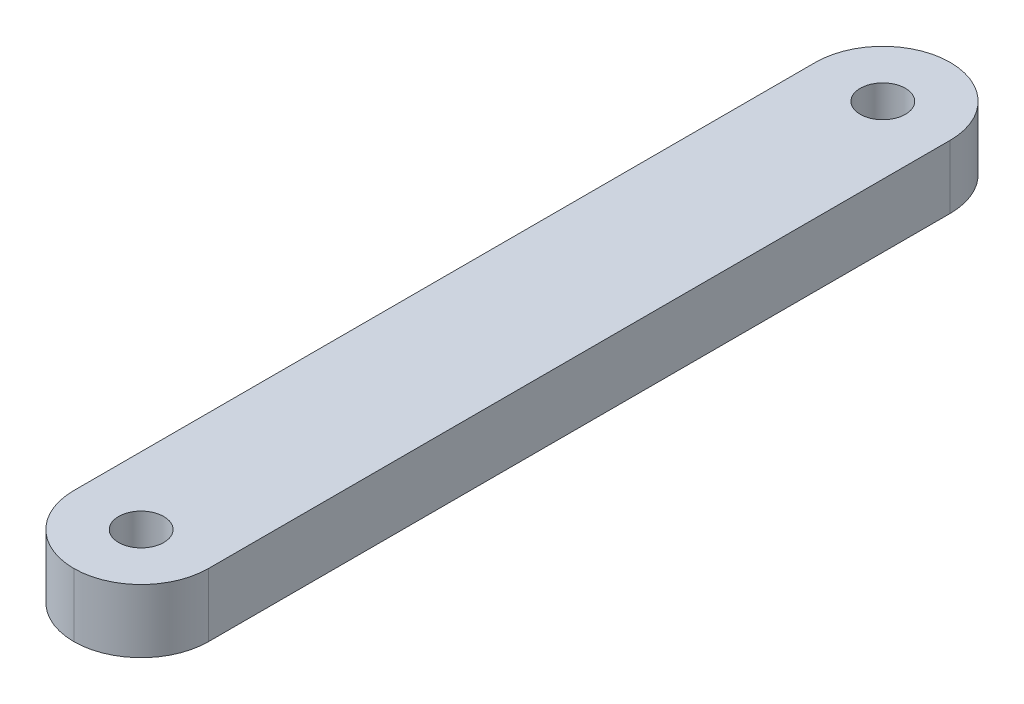
SolidWorks part; units mm, degrees
ref_plane "前视基准面" through (0, 0, 0) normal (0, 0, 1) x (1, 0, 0)
ref_plane "上视基准面" through (0, 0, 0) normal (0, 1, 0) x (1, 0, 0)
ref_plane "右视基准面" through (0, 0, 0) normal (1, 0, 0) x (0, 0, -1)
sketch "草图1" plane through (0, 0, 0) normal (0, 0, 1) x (1, 0, 0)
  line L1 (0, 0) -> (10, 0)
  line L2 (0, 0) -> (0, 5)
  line L3 (0, 5) -> (10, 5)
  line L4 (10, 0) -> (10, 5)
  dimension "D1" = 5
  dimension "D2" = 10
extrude "凸台-拉伸1" add sketch "草图1" along normal blind 65
sketch "草图2" plane through (0, 5, 0) normal (0, 1, 0) x (1, 0, 0)
  line L0 (10, 0) -> (0, 0) construction
  line L1 (10, -65) -> (10, 0) construction
  line L2 (10, -65) -> (0, -65) construction
  circle A0 centre (5, -5) radius 1.675
  circle A1 centre (5, -60) radius 1.675
  dimension "D1" = 3.35
  dimension "D2" = 3.35
  dimension "D3" = 5
  dimension "D4" = 5
  dimension "D5" = 5
  dimension "D6" = 5
extrude "切除-拉伸1" cut sketch "草图2" against normal blind 40
fillet "圆角1" radius 5 4 edges at (0, 2.5, 65) (10, 2.5, 65) (0, 2.5, 0) (10, 2.5, 0)
sketch "草图3" plane through (0, 5, 0) normal (0, 1, 0) x (1, 0, 0)
  line L1 (-7.1185, 5.0291) -> (29.7056, 5.0291)
  line L2 (-7.1185, 5.0291) -> (-7.1185, -73.172)
  line L3 (-7.1185, -73.172) -> (29.7056, -73.172)
  line L4 (29.7056, 5.0291) -> (29.7056, -73.172)
extrude "切除-拉伸2" cut sketch "草图3" against normal blind 0.3
